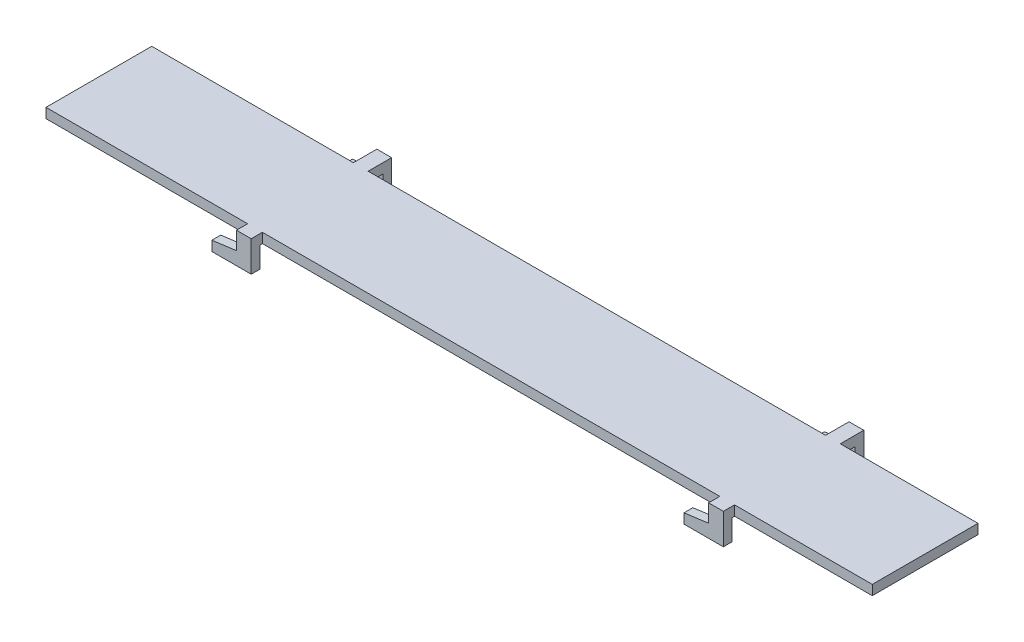
SolidWorks part; units mm, degrees
ref_plane "Top" through (0, 0, 0) normal (0, 0, 1) x (1, 0, 0)
ref_plane "Front" through (0, 0, 0) normal (0, 1, 0) x (1, 0, 0)
ref_plane "Right" through (0, 0, 0) normal (1, 0, 0) x (0, 0, -1)
sketch "Top Sketch" plane through (0, 0, 0) normal (0, 1, 0) x (1, 0, 0)
  line L0 (-28, -21.5) -> (-28, -22.875)
  line L1 (-168, 0) -> (-127, 0)
  line L2 (-168, 0) -> (-168, -21.5)
  line L3 (-168, -21.5) -> (-127, -21.5)
  line L4 (0, 0) -> (0, -21.5)
  line L5 (-28, -22.875) -> (-36, -22.875) construction
  line L6 (-36, -22.875) -> (-36, -21.5) construction
  line L7 (-124, -21.5) -> (-124, -22.875)
  line L8 (-124, -22.875) -> (-132, -22.875) construction
  line L9 (-132, -22.875) -> (-132, -21.5) construction
  line L10 (-28, 0) -> (-28, 3.875)
  line L11 (-28, 3.875) -> (-36, 3.875) construction
  line L12 (-36, 3.875) -> (-36, 0) construction
  line L13 (-124, 0) -> (-124, 3.875)
  line L14 (-124, 3.875) -> (-132, 3.875) construction
  line L15 (-132, 3.875) -> (-132, 0) construction
  line L16 (-28, 0) -> (0, 0)
  line L17 (-28, -21.5) -> (0, -21.5)
  line L18 (-124, 0) -> (-31, 0)
  line L19 (-124, -21.5) -> (-31, -21.5)
  line L20 (-31, 3.875) -> (-31, 0)
  line L21 (-31, 3.875) -> (-28, 3.875)
  line L22 (-31, -21.5) -> (-31, -22.875)
  line L23 (-31, -22.875) -> (-28, -22.875)
  line L24 (-127, 3.875) -> (-127, 0)
  line L25 (-127, 3.875) -> (-124, 3.875)
  line L26 (-127, -22.875) -> (-127, -21.5)
  line L27 (-127, -22.875) -> (-124, -22.875)
  line L28 (-168, -15.863) -> (0, -15.863) construction
  point P32 (-84, -15.863)
  dimension "D1" = 21.5
  dimension "Length" = 168
  dimension "D3" = 1.375
  dimension "D5" = 5
  dimension "D6" = 3.875
  dimension "D8" = 3
extrude "Thickness Extrude" add sketch "Top Sketch" along normal blind 2
sketch "Hook Sketch" plane through (0, 0, 22.875) normal (0, 0, 1) x (1, 0, 0)
  line L0 (-31, 2) -> (-28, 2)
  line L1 (-31, 0) -> (-28, 0) construction
  line L2 (-28, 2) -> (-28, -4.2583)
  line L3 (-28, -4.2583) -> (-36, -4.2583)
  line L4 (-36, -4.2583) -> (-36, -2.2583)
  line L5 (-36, -2.2583) -> (-31, -1.6)
  line L6 (-31, -1.6) -> (-31, 2)
  dimension "D1" = 7.5
  dimension "D2" = 5
  dimension "D3" = 1.6
  dimension "D4" = 2
extrude "Hook 1 Extrude" add sketch "Hook Sketch" against normal blind 0.9 and the other way blind 0.9 separate body
extrude "Hook 2 Extrude" add sketch "Hook Sketch<2>" along normal blind 0.9 and the other way blind 0.9 from surface separate body starting at face at (-29.5, 1, -3.875)
sketch "Hook Sketch<2>" plane through (0, 0, 22.875) normal (0, 0, 1) x (1, 0, 0) same geometry as "Hook Sketch"
pattern_linear "Hook Pattern" count 2 spacing 96 along (-1, 0, 0) of "Hook 1 Extrude", "Hook 2 Extrude"
combine bodies "Combine Bodies" operation type add bodies to combine 101 103 104 105 106
